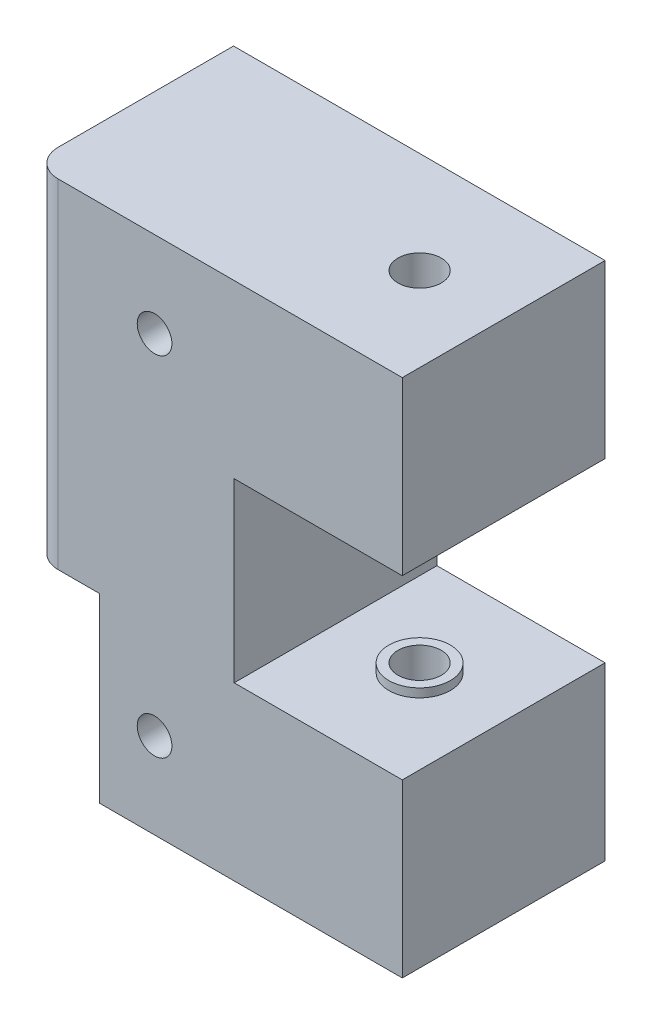
SolidWorks part; units mm, degrees
ref_plane "Front Plane" through (0, 0, 0) normal (0, 0, 1) x (1, 0, 0)
ref_plane "Top Plane" through (0, 0, 0) normal (0, 1, 0) x (1, 0, 0)
ref_plane "Right Plane" through (0, 0, 0) normal (1, 0, 0) x (0, 0, -1)
sketch "MainBlock" plane through (0, 0, 0) normal (0, 0, 1) x (1, 0, 0)
  line L0 (0, 0) -> (42.875, 0)
  line L1 (42.875, 0) -> (42.875, 19.8)
  line L2 (42.875, 19.8) -> (23.475, 19.8)
  line L3 (23.475, 19.8) -> (23.475, 40.2)
  line L4 (23.475, 40.2) -> (42.875, 40.2)
  line L5 (42.875, 40.2) -> (42.875, 60)
  line L6 (42.875, 60) -> (0, 60)
  line L7 (0, 60) -> (0, 0)
  circle A0 centre (14.2875, 50.1) radius 2
  circle A1 centre (14.2875, 9.9) radius 2
  dimension "D4" = 4
  dimension "D1" = 42.875
  dimension "D2" = 60
  dimension "D3" = 20.4
  dimension "D5" = 19.4
  dimension "D6" = 14.2875
  dimension "D7" = 9.9
  dimension "D9" = 19.8
  dimension "D10" = 19.8
  dimension "D8" = 40.2
  dimension "D11" = 9.9
extrude "MainBlockBoss-Extrude1" add sketch "MainBlock" along normal blind 23.4
sketch "TopHoleCut-Sketch2" plane through (0, 60, 0) normal (0, 1, 0) x (1, 0, 0)
  line L0 (42.875, 0) -> (0, 0) construction
  circle A0 centre (33.175, -11.7) radius 2.5
  dimension "D3" = 5
  dimension "D1" = 11.7
  dimension "D2" = 9.7
extrude "TopHoleCut-Extrude1" cut sketch "TopHoleCut-Sketch2" against normal blind 45
sketch "TopSpacerSketch4" plane through (0, 40.2, 0) normal (0, -1, 0) x (1, 0, 0)
  circle A0 centre (33.175, 11.7) radius 3.55
  circle A1 centre (33.175, 11.7) radius 2.5
  circle A2 centre (33.175, 11.7) radius 2.5 construction
  dimension "D1" = 7.1
extrude "TopSpacerBoss-Extrude2" add sketch "TopSpacerSketch4" along normal blind 1
sketch "LowerSpacerSketch5" plane through (0, 19.8, 0) normal (0, 1, 0) x (1, 0, 0)
  circle A0 centre (33.175, -11.7) radius 2.5
  circle A1 centre (33.175, -11.7) radius 2.5 construction
  circle A2 centre (33.175, -11.7) radius 3.55
  circle A3 centre (33.175, -11.7) radius 3.55 construction
extrude "LowerSpacerBoss-Extrude3" add sketch "LowerSpacerSketch5" along normal blind 1
sketch "MountHoleBoreSketch1" plane through (0, 0, 0) normal (0, 0, -1) x (-1, 0, 0)
  line L1 (-10.4125, 50.1) -> (-12.35, 53.4558)
  line L2 (-12.35, 53.4558) -> (-16.225, 53.4558)
  line L3 (-16.225, 53.4558) -> (-18.1625, 50.1)
  line L4 (-18.1625, 50.1) -> (-16.225, 46.7442)
  line L5 (-16.225, 46.7442) -> (-12.35, 46.7442)
  line L6 (-12.35, 46.7442) -> (-10.4125, 50.1)
  line L7 (-10.4125, 9.9) -> (-12.35, 13.2558)
  line L8 (-12.35, 13.2558) -> (-16.225, 13.2558)
  line L9 (-16.225, 13.2558) -> (-18.1625, 9.9)
  line L10 (-18.1625, 9.9) -> (-16.225, 6.5442)
  line L11 (-16.225, 6.5442) -> (-12.35, 6.5442)
  line L12 (-12.35, 6.5442) -> (-10.4125, 9.9)
  circle A0 centre (-14.2875, 50.1) radius 3.3558 construction
  circle A1 centre (-14.2875, 9.9) radius 3.3558 construction
  dimension "D1" = 7.75
extrude "MountHoleBoreCut-Extrude1" cut sketch "MountHoleBoreSketch1" against normal blind 2
sketch "PushPinHoleSketch1" plane through (0, 0, 0) normal (0, -1, 0) x (1, 0, 0)
  circle A0 centre (33.175, 11.7) radius 2
  circle A1 centre (33.175, 11.7) radius 2.5 construction
extrude "PushPinHoleCut-Extrude1" cut sketch "PushPinHoleSketch1" against normal through all
sketch "MidRailInsetSketch1" plane through (0, 0, 0) normal (0, 0, -1) x (-1, 0, 0)
  line L0 (0, 60) -> (0, 0) construction
  line L1 (0, 20.9498) -> (-7.9375, 20.9498)
  line L2 (0, 20.9498) -> (0, 0)
  line L3 (0, 0) -> (-7.9375, 0)
  line L4 (-7.9375, 20.9498) -> (-7.9375, 0)
  line L6 (0, 0) -> (-42.875, 0) construction
  line L7 (-42.875, 60) -> (0, 60) construction
  dimension "D1" = 7.9375
  dimension "D2" = 39.0502
extrude "MidRailInsetCut-Extrude2" cut sketch "MidRailInsetSketch1" against normal through all
fillet "VerticalSupportFillet1" radius 3.175 1 edges at (0, 40.4749, 23.4)
equation "\"BeltTensionerWidth\"= \"MidRailToAlignWithGantryBlock\" + \"BeltTensionerInnerWidth\" / 2 + \"RailThickness\""
equation "\"BeltTensionerHeight\"= 60mm"
equation "\"BeltTensionerInnerWidth\"= \"20TGT2PulleyDiameter\" + \"BeltTensionerSpaceBetweenPulleyAndWall\""
equation "\"BeltTensionerBackWallThickness\"= 4mm"
equation "\"RailThickness\"= .125in'Spec"
equation "\"HoleOffsetFromEdge\"= \"RailThickness\" * 2.5"
equation "\"MidRailToAlignWithGantryBlock\"= \"Nema17MountStepperHoleDistanceFromBack\"'All outside cogs must align"
equation "\"20TGT2PulleyDiameter\"= 17.9mm'Spec"
equation "\"BeltTensionerSpaceBetweenPulleyAndWall\"= 1.5mm"
equation "\"BeltTensionerMountingHoleDiameter\"= 4.0mm"
equation "\"BeltTensionerMountingHoleOffsetFromEdge\"= \"HoleOffsetFromEdge\" + \"RailThickness\" * 2"
equation "\"20TGT2PulleyWidth\"= 8.7mm'The STL of the Pulley in the diagram is a bit larger"
equation "\"1mmSpacer\"= 1mm"
equation "\"SteelShaft5mmHoleDiameter\"= 5mm"
equation "\"BeltTensionerMountingHoleOuterBoreDepth\"= 2mm"
equation "\"BeltTensionerMountingHoleOuterBoreDiameter\"= 7.75mm"
equation "\"7mmx1mmSpacerDiameter\"= 7mm + .1mm'Add .1mm for printing"
equation "\"7mmx1mmSpacerHeight\"= 1mm"
equation "\"D1@MainBlock\" = \"BeltTensionerWidth\""
equation "\"D4@MainBlock\" = \"BeltTensionerMountingHoleDiameter\""
equation "\"D5@MainBlock\" = \"BeltTensionerInnerWidth\""
equation "\"D6@MainBlock\" = \"BeltTensionerMountingHoleOffsetFromEdge\""
equation "\"D7@MainBlock\"=\"BeltTensionerMountingHoleOffsetFromTopOrBottom\""
equation "\"D1@MainBlockBoss-Extrude1\" = \"BeltTensionerDepth\""
equation "\"D1@TopHoleCut-Sketch2\" = \"BeltTensionerDepth\" / 2"
equation "\"D3@TopHoleCut-Sketch2\" = \"SteelShaft5mmHoleDiameter\""
equation "\"D1@TopSpacerSketch4\" = \"7mmx1mmSpacerDiameter\""
equation "\"D1@TopSpacerBoss-Extrude2\" = \"7mmx1mmSpacerHeight\""
equation "\"D1@LowerSpacerBoss-Extrude3\" = \"7mmx1mmSpacerHeight\""
equation "\"D1@MountHoleBoreSketch1\" = \"BeltTensionerMountingHoleOuterBoreDiameter\""
equation "\"D1@MountHoleBoreCut-Extrude1\" = \"BeltTensionerMountingHoleOuterBoreDepth\""
equation "\"SteelPushPinHoleDiameter\"= \"SteelShaft5mmHoleDiameter\" - 1mm"
equation "\"D1@PushPinHoleSketch1\" = \"SteelPushPinHoleDiameter\""
equation "\"D2@TopHoleCut-Sketch2\"=\"BeltTensionerWidth\" - \"MidRailToAlignWithGantryBlock\" - \"RailThickness\""
equation "\"BeltTensionerMountingHoleOffsetFromTopOrBottom\"= ( \"BeltTensionerHeight\" - \"BeltTensionerInnerHeight\" ) / 4"
equation "\"SteelShaftLength\"= 30mm"
equation "\"D1@TopHoleCut-Extrude1\"=\"BeltTensionerSteelShaftHoleDepthFromTop\""
equation "\"D2@MidRailInsetSketch1\"=\"DistanceAboveMidSideRailToTopOfBeltTensioner\""
equation "\"DistanceAboveMidSideRailToTopOfBeltTensioner\"= \"VSBeltTensionerY1ToAlignWithYAxisGantryUpperPulleyYSValue\" + \"BeltTensionerMountingHoleOffsetFromTopOrBottom\" - \"V8 ToTopOfMidSideRailYSValue\"'Equals 39.05017"
equation "\"D3@MainBlock\"=\"BeltTensionerInnerHeight\""
equation "\"D9@MainBlock\"=\"BeltTensionerTopHeight\""
equation "\"V8 ToTopOfMidSideRailYSValue\"= 376.9847mm"
equation "\"D1@VerticalSupportFillet1\"=\"RailThickness\""
equation "\"D1@MidRailInsetSketch1\"=\"HoleOffsetFromEdge\""
equation "\"BeltTensionerDistanceBetweenMountingHoles\"= \"BeltTensionerHeight\" - \"BeltTensionerMountingHoleOffsetFromTopOrBottom\" * 2'Equals 40.2"
equation "\"D2@MainBlock\"=\"BeltTensionerHeight\""
equation "\"D8@MainBlock\" = \"BeltTensionerDistanceBetweenMountingHoles\""
equation "\"VSBeltTensionerY1ToAlignWithYAxisGantryUpperPulleyYSValue\"= 406.13487mm"
equation "\"BeltTensionerDepth\"= \"BeltTensionerBackWallThickness\" + \"BeltTensionerInnerDepth\"'Equals 23.4"
equation "\"BeltTensionerInnerHeight\"= \"20TGT2PulleyWidth\" * 2 + \"1mmSpacer\" * 3"
equation "\"BeltTensionerTopHeight\"= ( \"BeltTensionerHeight\" - \"BeltTensionerInnerHeight\" ) / 2'Equals 19.8"
equation "\"BeltTensionerSteelShaftHoleDepthFromTop\"= ( \"SteelShaftLength\" - \"BeltTensionerInnerHeight\" ) / 2 + ( \"BeltTensionerHeight\" - \"BeltTensionerInnerHeight\" ) / 2 + \"BeltTensionerInnerHeight\"'Equals 45"
equation "\"BeltTensionerInnerDepth\"= \"20TGT2PulleyDiameter\" + \"BeltTensionerSpaceBetweenPulleyAndWall\"'Equals 19.4"
equation "\"Nema17MountStepperHoleDistanceFromBack\"= 30mm'Spec"
